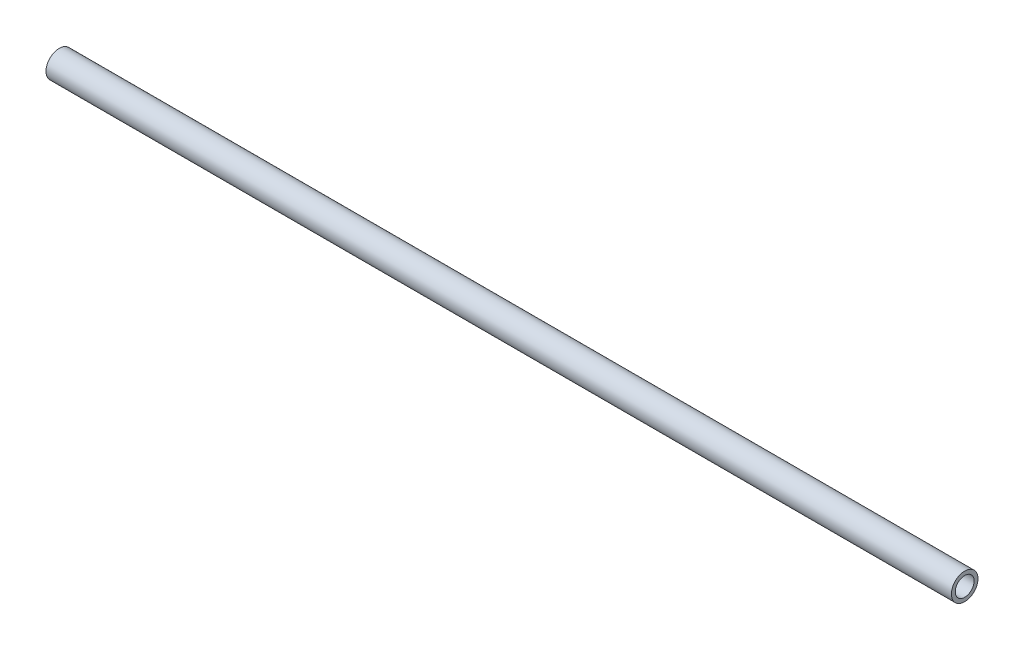
SolidWorks part; units mm, degrees
ref_plane "Front Plane" through (0, 0, 0) normal (0, 0, 1) x (1, 0, 0)
ref_plane "Top Plane" through (0, 0, 0) normal (0, 1, 0) x (1, 0, 0)
ref_plane "Right Plane" through (0, 0, 0) normal (1, 0, 0) x (0, 0, -1)
sketch "Sketch1" plane through (0, 0, 0) normal (1, 0, 0) x (0, 0, -1)
  circle A0 centre (0, 0) radius 8.9535
  circle A1 centre (0, 0) radius 6.35
  dimension "D1" = 17.907
  dimension "D2" = 12.7
extrude "Boss-Extrude1" add sketch "Sketch1" along normal blind 304.8 and the other way blind 304.8
